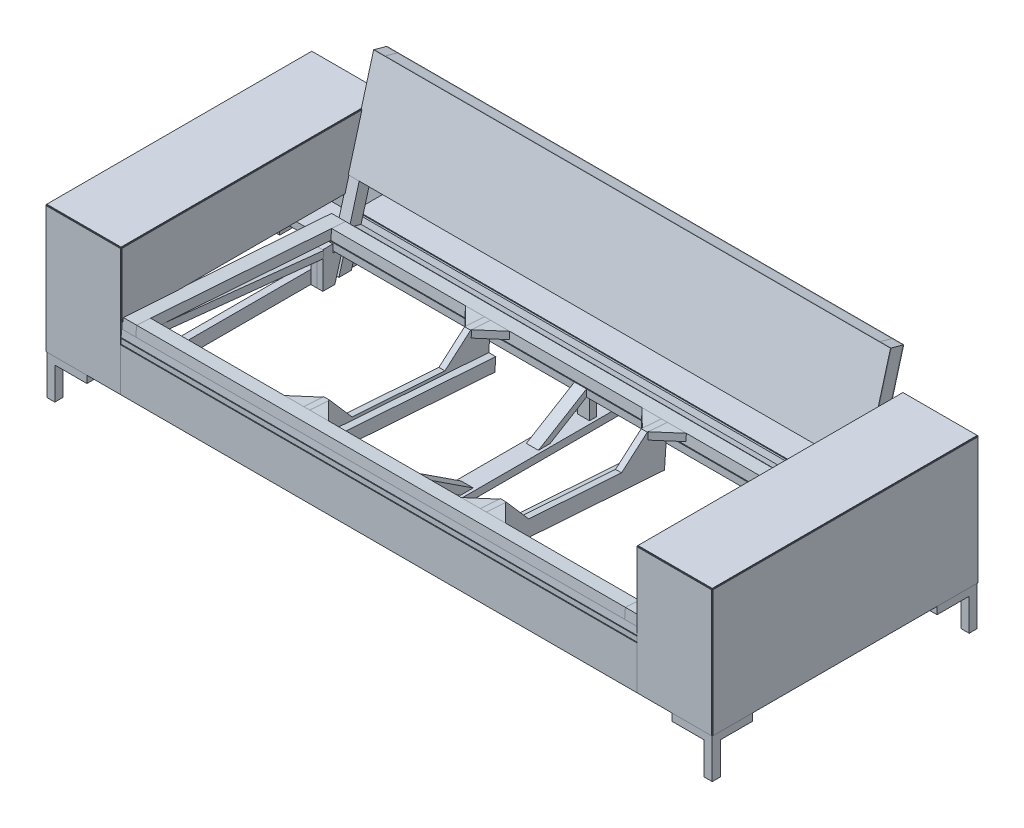
SolidWorks part; units mm, degrees
note: The reader was unsure of these and kept them because the rebuilt part matched: shared geometry of "Sketch1<3>", "Sketch1<4>", "Sketch1<5>", "Sketch4<3>", "Sketch4<4>", "Sketch5<3>", "Sketch5<12>", "Sketch5<4>", "Sketch5<5>", "Sketch5<7>", "Sketch5<8>", "Sketch5<9>", "Sketch5<10>", "Sketch5<11>", "Sketch12<3>", "Sketch14<3>", "Sketch16<3>", "Sketch13<3>", "Sketch13<4>".
other "Foot" parameters "D1"=20.7649, "D2"=44.1105, "D3"=41.275, "D4"=234.95, "D5"=234.95, "D6"=234.95, "D7"=41.275, "D8"=60.325
material "Balsa"
ref_plane "Front Plane" through (0, 0, 0) normal (0, 0, 1) x (1, 0, 0)
ref_plane "Top Plane" through (0, 0, 0) normal (0, 1, 0) x (1, 0, 0)
ref_plane "Right Plane" through (0, 0, 0) normal (1, 0, 0) x (0, 0, -1)
sketch "Sketch1" plane through (0, 0, 0) normal (0, 0, 1) x (1, 0, 0)
  line L0 (0, 0) -> (0, 288750.7845) construction
  line L1 (-817.5625, 0) -> (-1052.5125, 0) construction
  line L2 (-817.5625, 0) -> (-817.5625, 400.05) construction
  line L3 (-817.5625, 400.05) -> (-1052.5125, 400.05) construction
  line L4 (-1052.5125, 0) -> (-1052.5125, 400.05) construction
  line L5 (-1030.2875, 358.775) -> (-1030.2875, 219.075) construction
  line L6 (-1052.5125, 400.05) -> (-1030.2875, 400.05)
  line L7 (-1052.5125, 400.05) -> (-1052.5125, 358.775)
  line L8 (-1052.5125, 358.775) -> (-1030.2875, 358.775)
  line L9 (-1030.2875, 400.05) -> (-1030.2875, 358.775)
  line L10 (-955.675, 400.05) -> (-914.4, 400.05)
  line L11 (-955.675, 400.05) -> (-955.675, 377.825)
  line L12 (-955.675, 377.825) -> (-914.4, 377.825)
  line L13 (-914.4, 400.05) -> (-914.4, 377.825)
  line L14 (-817.5625, 400.05) -> (-839.7875, 400.05)
  line L15 (-817.5625, 400.05) -> (-817.5625, 358.775)
  line L16 (-817.5625, 358.775) -> (-839.7875, 358.775)
  line L17 (-839.7875, 400.05) -> (-839.7875, 358.775)
  line L18 (-1052.5125, 196.85) -> (-1030.2875, 196.85)
  line L19 (-1052.5125, 196.85) -> (-1052.5125, 219.075)
  line L20 (-1052.5125, 219.075) -> (-1030.2875, 219.075)
  line L21 (-1030.2875, 196.85) -> (-1030.2875, 219.075)
  line L22 (-817.5625, 196.85) -> (-839.7875, 196.85)
  line L23 (-817.5625, 196.85) -> (-817.5625, 219.075)
  line L24 (-817.5625, 219.075) -> (-839.7875, 219.075)
  line L25 (-839.7875, 196.85) -> (-839.7875, 219.075)
  line L26 (-1052.5125, 0) -> (-1030.2875, 0)
  line L27 (-1052.5125, 0) -> (-1052.5125, 41.275)
  line L28 (-1052.5125, 41.275) -> (-1030.2875, 41.275)
  line L29 (-1030.2875, 0) -> (-1030.2875, 41.275)
  line L30 (-817.5625, 0) -> (-839.7875, 0)
  line L31 (-817.5625, 0) -> (-817.5625, 41.275)
  line L32 (-817.5625, 41.275) -> (-839.7875, 41.275)
  line L33 (-839.7875, 0) -> (-839.7875, 41.275)
  line L34 (-1030.2875, 196.85) -> (-1030.2875, 41.275) construction
  line L35 (-839.7875, 41.275) -> (-839.7875, 196.85) construction
  line L36 (-839.7875, 219.075) -> (-839.7875, 358.775) construction
  line L37 (-1052.5125, 0) -> (-1052.5125, 400.05)
  line L38 (-839.7875, 0) -> (-1030.2875, 0)
  line L39 (-839.7875, 0) -> (-839.7875, 22.225)
  line L40 (-839.7875, 22.225) -> (-1030.2875, 22.225)
  line L41 (-1030.2875, 0) -> (-1030.2875, 22.225)
  line L42 (-817.5625, 400.05) -> (-1052.5125, 400.05)
  line L43 (-817.5625, 400.05) -> (-817.5625, 196.85)
  point P34 (-935.0375, 400.05)
  dimension "D1" = 22.225
  dimension "D2" = 41.275
  dimension "D3" = 190.5
  dimension "D4" = 400.05
  dimension "D5" = 196.85
  dimension "D6" = 1679.575
  dimension "D7" = 22.225
extrude "Boss-Extrude1" add sketch "Sketch1" along normal blind 838.2 contours L9 L6 L7 L8 | L13 L10 L11 L12 | L14 L17 L16 L15 | L25 L22 L23 L24 | L33 L30 L31 L32 | L26 L29 L28 L27 | L18 L21 L20 L19
extrude "Extrude-Thin1" add sketch "Sketch1<3>" along normal up to surface (838.2 mm away) separate body thin contours L42
sketch "Sketch1<3>" plane through (0, 0, 0) normal (0, 0, 1) x (1, 0, 0) same geometry as "Sketch1"
extrude "Extrude-Thin2" add sketch "Sketch1<4>" along normal up to surface (838.2 mm away) separate body thin contours L37
sketch "Sketch1<4>" plane through (0, 0, 0) normal (0, 0, 1) x (1, 0, 0) same geometry as "Sketch1"
extrude "Extrude-Thin3" add sketch "Sketch1<5>" along normal blind 838.2 separate body thin contours L43
sketch "Sketch1<5>" plane through (0, 0, 0) normal (0, 0, 1) x (1, 0, 0) same geometry as "Sketch1"
sketch "Sketch2" plane through (-817.5625, 0, 0) normal (-1, 0, 0) x (0, 0, 1)
  line L0 (0, 219.075) -> (139.7, 219.075)
  line L1 (838.2, 219.075) -> (0, 219.075) construction
  line L2 (139.7, 219.075) -> (95.25, 358.775)
  line L3 (838.2, 358.775) -> (0, 358.775) construction
  line L4 (95.25, 358.775) -> (0, 358.775)
  line L5 (0, 358.775) -> (0, 219.075)
  dimension "D1" = 95.25
  dimension "D2" = 139.7
extrude "Boss-Extrude2" add sketch "Sketch2" along normal up to surface (22.225 mm away) separate body up to face at (-839.7875, 207.9625, 419.1)
sketch "Sketch3" plane through (0, 400.05, 0) normal (0, -1, 0) x (1, 0, 0)
  line L0 (-839.7875, 838.2) -> (-839.7875, 0) construction
  line L1 (-839.7875, 241.3) -> (-914.4, 241.3)
  line L2 (-839.7875, 241.3) -> (-839.7875, 282.575)
  line L3 (-839.7875, 282.575) -> (-914.4, 282.575)
  line L4 (-914.4, 241.3) -> (-914.4, 282.575)
  line L5 (-914.4, 838.2) -> (-914.4, 0) construction
  line L6 (-955.675, 838.2) -> (-955.675, 0) construction
  line L7 (-955.675, 241.3) -> (-1030.2875, 241.3)
  line L8 (-955.675, 241.3) -> (-955.675, 282.575)
  line L9 (-955.675, 282.575) -> (-1030.2875, 282.575)
  line L10 (-1030.2875, 241.3) -> (-1030.2875, 282.575)
  line L11 (-817.5625, 0) -> (-1052.5125, 0) construction
  line L12 (-839.7875, 584.2) -> (-914.4, 584.2)
  line L13 (-839.7875, 584.2) -> (-839.7875, 625.475)
  line L14 (-839.7875, 625.475) -> (-914.4, 625.475)
  line L15 (-914.4, 584.2) -> (-914.4, 625.475)
  line L16 (-955.675, 584.2) -> (-1030.2875, 584.2)
  line L17 (-955.675, 584.2) -> (-955.675, 625.475)
  line L18 (-955.675, 625.475) -> (-1030.2875, 625.475)
  line L19 (-1030.2875, 584.2) -> (-1030.2875, 625.475)
  line L20 (-1030.2875, 838.2) -> (-1030.2875, 0) construction
  dimension "D1" = 241.3
  dimension "D2" = 584.2
  dimension "D3" = 41.275
extrude "Boss-Extrude3" add sketch "Sketch3" along normal up to surface (22.225 mm away) separate body up to face at (-935.0375, 377.825, 419.1)
sketch "Sketch4" plane through (0, 0, 0) normal (0, -1, 0) x (1, 0, 0)
  line L0 (-839.7875, 838.2) -> (-839.7875, 0) construction
  line L1 (-1030.2875, 838.2) -> (-839.7875, 838.2)
  line L2 (-1030.2875, 838.2) -> (-1030.2875, 727.075)
  line L3 (-1030.2875, 727.075) -> (-839.7875, 727.075)
  line L4 (-839.7875, 838.2) -> (-839.7875, 727.075)
  line L5 (-1030.2875, 838.2) -> (-1030.2875, 0) construction
  line L6 (-839.7875, 0) -> (-1030.2875, 0)
  line L7 (-839.7875, 0) -> (-839.7875, 111.125)
  line L8 (-839.7875, 111.125) -> (-1030.2875, 111.125)
  line L9 (-1030.2875, 0) -> (-1030.2875, 111.125)
  line L10 (-817.5625, 838.2) -> (-1052.5125, 838.2)
  line L11 (-817.5625, 0) -> (-1052.5125, 0)
  line M3 (-1030.2875, 0) -> (-1030.2875, 838.2)
  dimension "D1" = 111.125
extrude "Boss-Extrude4" add sketch "Sketch4" against normal blind 22.225 separate body contours L7 L8 L6 M3 | L4 L1 L3 M3
extrude "Extrude-Thin4" add sketch "Sketch4<3>" against normal up to surface (400.05 mm away) separate body thin contours L10
sketch "Sketch4<3>" plane through (0, 0, 0) normal (0, -1, 0) x (1, 0, 0) same geometry as "Sketch4"
extrude "Extrude-Thin5" add sketch "Sketch4<4>" against normal up to surface (400.05 mm away) separate body thin contours L11
sketch "Sketch4<4>" plane through (0, 0, 0) normal (0, -1, 0) x (1, 0, 0) same geometry as "Sketch4"
mirror "Mirror Arm Geo" about plane through (0, 0, 0) normal (1, 0, 0) of bodies 115 134 103 107 114 104 137 108 135 109 113 111 105 101 133 102 106 110 112
ref_plane "Plane1" through (0, 0, 419.1) normal (0, 0, 1) x (1, 0, 0)
sketch "Sketch5" plane through (-817.5625, 0, 0) normal (1, 0, 0) x (0, 0, -1)
  line L0 (-79.375, 124.2618) -> (-90.3567, 84.4745)
  line L1 (0, 0) -> (-238.125, 0)
  line L2 (0, 0) -> (0, 130.175)
  line L3 (0, 130.175) -> (-238.125, 130.175)
  line L4 (-238.125, 0) -> (-238.125, 130.175)
  line L5 (0, 22.225) -> (-41.275, 22.225)
  line L6 (0, 22.225) -> (0, 0)
  line L7 (0, 0) -> (-41.275, 0)
  line L8 (-41.275, 22.225) -> (-41.275, 0)
  line L9 (0, 130.175) -> (-22.225, 130.175)
  line L10 (0, 130.175) -> (0, 88.9)
  line L11 (0, 88.9) -> (-22.225, 88.9)
  line L12 (-22.225, 130.175) -> (-22.225, 88.9)
  line L13 (-202.474, 91.9539) -> (-161.199, 91.9539)
  line L14 (-202.474, 91.9539) -> (-202.474, 114.1789)
  line L15 (-202.474, 114.1789) -> (-161.199, 114.1789)
  line L16 (-161.199, 91.9539) -> (-161.199, 114.1789)
  line L17 (-79.375, 124.2618) -> (-100.7989, 130.175)
  line L18 (-90.3567, 84.4745) -> (-111.7806, 90.3877)
  line L19 (-100.7989, 130.175) -> (-111.7806, 90.3877)
  line L20 (-144.4255, 9.525) -> (-183.9502, 9.525)
  line L21 (-183.9502, 9.525) -> (-150.6496, 130.175)
  line L22 (-150.6496, 130.175) -> (-113.9229, 120.0381)
  line L23 (-113.9229, 120.0381) -> (-144.4255, 9.525)
  line L24 (-113.9229, 120.0381) -> (-124.9046, 80.2508)
  line L25 (-124.9046, 80.2508) -> (-146.3285, 86.164)
  line L26 (-146.3285, 86.164) -> (-135.3468, 125.9513)
  line L27 (-135.3468, 125.9513) -> (-113.9229, 120.0381)
  line L28 (-200.025, 0) -> (-174.625, 88.9)
  line L29 (-174.625, 88.9) -> (-206.375, 88.9)
  line L30 (-206.375, 88.9) -> (-206.375, 114.1789)
  line L31 (-206.375, 114.1789) -> (-238.125, 114.1789)
  line L32 (-838.2, 0) -> (-838.2, 136.525)
  line L33 (-838.2, 0) -> (-815.975, 0)
  line L34 (-838.2, 0) -> (-838.2, 41.275)
  line L35 (-838.2, 41.275) -> (-815.975, 41.275)
  line L36 (-815.975, 0) -> (-815.975, 41.275)
  line L37 (-838.2, 400.05) -> (-838.2, 196.85) construction
  line L38 (-838.2, 196.85) -> (-838.2, 219.075) construction
  line L39 (-838.2, 154.7295) -> (-240.4418, 92.075)
  line L40 (-815.975, 111.125) -> (-838.2, 111.125)
  line L41 (-815.975, 111.125) -> (-815.975, 152.4)
  line L42 (-815.975, 152.4) -> (-838.2, 152.4)
  line L43 (-838.2, 111.125) -> (-838.2, 152.4)
  line L44 (-838.2, 154.7295) -> (-835.8832, 176.8334)
  line L45 (-240.4418, 92.075) -> (-238.125, 114.1789)
  line L46 (-835.8832, 176.8334) -> (-238.125, 114.1789)
  line L47 (-838.2, 400.05) -> (-838.2, 0) construction
  line L48 (-838.2, 0) -> (0, 0) construction
  line L49 (-815.975, 12.7) -> (-793.75, 12.7)
  line L50 (-815.975, 12.7) -> (-815.975, 150.0705)
  line L51 (-815.975, 150.0705) -> (-793.75, 150.0705)
  line L52 (-793.75, 12.7) -> (-793.75, 150.0705)
  line L53 (-835.8832, 176.8334) -> (-174.625, 130.175)
  line L54 (-835.8832, 176.8334) -> (-833.6429, 208.5834)
  line L55 (-174.625, 130.175) -> (-172.3847, 161.925)
  line L56 (-833.6429, 208.5834) -> (-172.3847, 161.925)
  line L57 (-838.2, 154.7295) -> (-797.1499, 150.4268)
  line L58 (-838.2, 154.7295) -> (-835.8832, 176.8334)
  line L59 (-797.1499, 150.4268) -> (-794.833, 172.5307)
  line L60 (-835.8832, 176.8334) -> (-794.833, 172.5307)
  line L61 (-150.6496, 130.175) -> (-36.7267, 542.925)
  line L62 (-36.7267, 542.925) -> (0, 532.7881)
  line L63 (0, 532.7881) -> (-113.9229, 120.0381)
  line L64 (0, 0) -> (0, 500.445) construction
  line L65 (-838.2, 400.05) -> (0, 400.05) construction
  line L66 (-838.2, 0) -> (0, 0) construction
  point P53 (-107.1867, 130.175)
  point P68 (-192.0022, 91.1104)
  point P69 (-203.7209, 112.4876)
  point P70 (-111.125, 130.175)
  point P71 (0, 0)
  point P72 (-174.625, 130.175)
  point P73 (-238.125, 113.2691)
  line M26 (0, 0) -> (0, 41.275)
  line M27 (0, 41.275) -> (-838.2, 41.275)
  line M28 (-838.2, 41.275) -> (-838.2, 0)
  line M29 (-838.2, 0) -> (0, 0)
  dimension "D1" = 238.125
  dimension "D2" = 130.175
  dimension "D3" = 22.225
  dimension "D4" = 111.125
  dimension "D5" = 142.875
  dimension "D6" = 88.9
  dimension "D7" = 31.75
  dimension "D8" = 38.1
  dimension "D9" = 41.275
  dimension "D10" = 57.15
  dimension "D11" = 9.525
  dimension "D12" = 31.75
  dimension "D13" = 38.1
  dimension "D14" = 92.075
  dimension "D15" = 136.525
  dimension "D16" = 152.4
  dimension "D17" = 12.7
  dimension "D18" = 31.75
  dimension "D19" = 41.275
extrude "Boss-Extrude6" add sketch "Sketch5" along normal blind 19.05 separate body contours L28 L4 M29 M27 | L30 L31 L4 L28 L29 M27 | L28 L1 L8 L5 L2 L23 L20 L21 M27 | L23 L21 L20 M27 | L25 L26 L22 L21 L23 M27 | L31 L30 L29 L28 L21 L13 L14 L15 L16 L3 L4 M27 | L13 L16 L15 L14 | L17 L19 L18 L0 | L26 L25 L23 L22 | L22 L23 L2 L11 L12 L3 L17 L0 L18 L19 M27 | L3 L12 L11 L2 | L5 L8 L1 M26
extrude "Boss-Extrude7" add sketch "Sketch5<3>" along normal blind 19.05 from surface at 19.05 separate body contours L28 L4 M29 M27 | L30 L31 L4 L28 L29 M27 starting at face at (-798.5125, 91.534, 121.7068)
sketch "Sketch5<3>" plane through (-817.5625, 0, 0) normal (1, 0, 0) x (0, 0, -1) same geometry as "Sketch5"
extrude "Boss-Extrude20" add sketch "Sketch5<12>" along normal blind 34.925 separate body contours L63 L62 L61 L3 | L26 L25 L23 L22 | L25 L26 L22 L21 L23 M27 | L23 L21 L20 M27 | L63 L3 L22
sketch "Sketch5<12>" plane through (-817.5625, 0, 0) normal (1, 0, 0) x (0, 0, -1) same geometry as "Sketch5"
extrude "Boss-Extrude9" add sketch "Sketch5<4>" along normal offset from surface (1597.025 mm away) 19.05 from surface at 19.05 separate body contours L5 L8 L1 M26 | L3 L12 L11 L2 | L17 L19 L18 L0 | L13 L16 L15 L14
sketch "Sketch5<4>" plane through (-817.5625, 0, 0) normal (1, 0, 0) x (0, 0, -1) same geometry as "Sketch5"
extrude "Boss-Extrude10" add sketch "Sketch5<5>" along normal offset from surface (1562.1 mm away) 19.05 from surface at 34.925 separate body contours L26 L25 L23 L22 up to face at (798.5125, 107.3248, 95.5778) starting at face at (-782.6375, 273.6908, 91.2756)
sketch "Sketch5<5>" plane through (-817.5625, 0, 0) normal (1, 0, 0) x (0, 0, -1) same geometry as "Sketch5"
extrude "Boss-Extrude11" add sketch "Sketch5<7>" along normal up to surface (1635.125 mm away) separate body contours L36 M29 M27 M28 | L43 L32 L40 L41 L42 | L39 L59 L46 L44 up to face at (817.5625, 20.6375, 419.1)
sketch "Sketch5<7>" plane through (-817.5625, 0, 0) normal (1, 0, 0) x (0, 0, -1) same geometry as "Sketch5"
extrude "Boss-Extrude13" add sketch "Sketch5<8>" along normal blind 41.275 separate body contours L52 L51 L41 L50 M27 | L49 L52 L36 M27
sketch "Sketch5<8>" plane through (-817.5625, 0, 0) normal (1, 0, 0) x (0, 0, -1) same geometry as "Sketch5"
extrude "Extrude-Thin6" add sketch "Sketch5<9>" along normal up to surface (1635.125 mm away) separate body thin contours L32
sketch "Sketch5<9>" plane through (-817.5625, 0, 0) normal (1, 0, 0) x (0, 0, -1) same geometry as "Sketch5"
extrude "Boss-Extrude14" add sketch "Sketch5<10>" along normal blind 41.275 separate body contours L46 L44 L39 L45
sketch "Sketch5<10>" plane through (-817.5625, 0, 0) normal (1, 0, 0) x (0, 0, -1) same geometry as "Sketch5"
extrude "Boss-Extrude15" add sketch "Sketch5<11>" along normal blind 44.45 separate body contours L54 L56 L55 L53
sketch "Sketch5<11>" plane through (-817.5625, 0, 0) normal (1, 0, 0) x (0, 0, -1) same geometry as "Sketch5"
mirror "Mirror2" about plane through (0, 0, 0) normal (1, 0, 0) of bodies 142 144 160 164 166 185 145
sketch "Sketch7" plane through (0, 149.0196, -10.5148) normal (0, 0.9975, -0.0704) x (1, 0, 0)
  line L0 (-773.1125, -846.2565) -> (-773.1125, -183.3543) construction
  line L1 (-773.1125, -846.2565) -> (773.1125, -846.2565)
  line L2 (-773.1125, -846.2565) -> (-773.1125, -801.8065)
  line L3 (-773.1125, -801.8065) -> (773.1125, -801.8065)
  line L4 (773.1125, -846.2565) -> (773.1125, -801.8065)
  line L5 (773.1125, -183.3543) -> (-773.1125, -183.3543)
  line L6 (773.1125, -183.3543) -> (773.1125, -227.8043)
  line L7 (773.1125, -227.8043) -> (-773.1125, -227.8043)
  line L8 (-773.1125, -183.3543) -> (-773.1125, -227.8043)
  line L9 (773.1125, -846.2565) -> (773.1125, -183.3543) construction
  dimension "D1" = 44.45
extrude "Boss-Extrude16" add sketch "Sketch7" against normal up to surface (31.8289 mm away) separate body up to face at (795.3375, 153.5042, 505.2541)
sketch "Sketch8" plane through (-817.5625, 0, 0) normal (-1, 0, 0) x (0, 0, 1)
  line L0 (0, 0) -> (0, 130.175)
  line L1 (0, 0) -> (0, 400.05) construction
  line L2 (0, 130.175) -> (95.25, 130.175)
  line L3 (0, 400.05) -> (0, 0) construction
  line L4 (0, 130.175) -> (111.125, 130.175) construction
  point P6 (0, 132.4753)
  dimension "D1" = 95.25
extrude "Extrude-Thin9" add sketch "Sketch8" against normal up to surface (1635.125 mm away) separate body thin contours L0 L2 up to face at (817.5625, 91.534, 121.7068) thin type one direction reverse wall 2.54
sketch "Sketch12" plane through (-817.5625, 0, 0) normal (-1, 0, 0) x (0, 0, 1)
  line L0 (36.7267, 542.925) -> (42.6399, 521.5011)
  line L1 (183.9502, 9.525) -> (36.7267, 542.925) construction
  line L2 (42.6399, 521.5011) -> (5.9132, 511.3641)
  line L3 (0, 532.7881) -> (144.4255, 9.525) construction
  line L4 (5.9132, 511.3641) -> (0, 532.7881)
  line L5 (0, 532.7881) -> (36.7267, 542.925)
  line L6 (119.5116, 242.99) -> (113.5984, 264.414)
  line L7 (113.5984, 264.414) -> (76.8717, 254.277)
  line L8 (76.8717, 254.277) -> (82.7849, 232.8531)
  line L9 (82.7849, 232.8531) -> (119.5116, 242.99)
  line L10 (119.5116, 242.99) -> (36.7267, 542.925)
  line L11 (0, 532.7881) -> (82.7849, 232.8531)
  line M5 (0, 532.7881) -> (144.4255, 9.525)
  line M7 (183.9502, 9.525) -> (36.7267, 542.925)
  line M8 (36.7267, 542.925) -> (0, 532.7881)
  dimension "D1" = 22.225
  dimension "D2" = 311.15
extrude "Boss-Extrude21" add sketch "Sketch12" against normal up to surface (1565.275 mm away) from surface at -34.925 separate body contours L9 L7 M5 M7 | L2 M7 M8 M5 up to face at (782.6375, 273.6908, 91.2756) starting at face at (-782.6375, 273.6908, 91.2756)
extrude "Extrude-Thin11" add sketch "Sketch12<3>" against normal up to surface (1635.125 mm away) separate body thin contours L10 | L11
sketch "Sketch12<3>" plane through (-817.5625, 0, 0) normal (-1, 0, 0) x (0, 0, 1) same geometry as "Sketch12"
ref_plane "Plane2" through (-269.875, 0, 0) normal (1, 0, 0) x (0, 0, -1)
sketch "Sketch14" plane through (-269.875, 0, 0) normal (1, 0, 0) x (0, 0, -1)
  line L0 (-789.3031, 205.4548) -> (-798.242, 78.7698)
  line L1 (-798.242, 78.7698) -> (-225.6634, 38.3686)
  line L2 (-225.6634, 38.3686) -> (-216.7245, 165.0536)
  line L3 (-216.7245, 165.0536) -> (-280.067, 169.5231)
  line L4 (-833.6429, 208.5834) -> (-172.3847, 161.925) construction
  line L5 (-280.067, 169.5231) -> (-361.4414, 98.8754)
  line L6 (-361.4414, 98.8754) -> (-655.3129, 119.611)
  line L7 (-655.3129, 119.611) -> (-725.9606, 200.9854)
  line L8 (-725.9606, 200.9854) -> (-789.3031, 205.4548)
  line L9 (-511.9527, 58.5692) -> (-508.3771, 109.2432) construction
  line L10 (-798.242, 78.7698) -> (-225.6634, 38.3686)
  line L11 (-798.242, 78.7698) -> (-795.3369, 119.9424)
  line L12 (-225.6634, 38.3686) -> (-222.7582, 79.5412)
  line L13 (-795.3369, 119.9424) -> (-222.7582, 79.5412)
  dimension "D1" = 127
  dimension "D2" = 50.8
  dimension "D3" = 45
  dimension "D4" = 63.5
  dimension "D5" = 41.275
extrude "Boss-Extrude25" add sketch "Sketch14" against normal blind 19.05 separate body contours L13 L9 L6 L7 L8 L0 | L1 L9 L13 L0 | L9 L10 L2 L13 | L9 L13 L2 L3 L5 L6
extrude "Boss-Extrude26" add sketch "Sketch14<3>" along normal blind 22.225 separate body contours L1 L9 L13 L0 | L9 L10 L2 L13
sketch "Sketch14<3>" plane through (-269.875, 0, 0) normal (1, 0, 0) x (0, 0, -1) same geometry as "Sketch14"
sketch "Sketch15" plane through (0, 149.0196, -10.5148) normal (0, 0.9975, -0.0704) x (1, 0, 0)
  line L0 (-288.925, -227.8043) -> (-349.25, -227.8043)
  line L1 (-773.1125, -227.8043) -> (773.1125, -227.8043) construction
  line L2 (-349.25, -227.8043) -> (-288.925, -288.1293)
  line L3 (-288.925, -291.3043) -> (-288.925, -367.5043) construction
  line L4 (-288.925, -288.1293) -> (-288.925, -227.8043)
  line L5 (-269.875, -227.8043) -> (-209.55, -227.8043)
  line L6 (-209.55, -227.8043) -> (-269.875, -288.1293)
  line L8 (-269.875, -288.1293) -> (-269.875, -227.8043)
  line L9 (-269.875, -801.8065) -> (-269.875, -741.4815)
  line L10 (-269.875, -662.1065) -> (-269.875, -738.3065) construction
  line L11 (-269.875, -741.4815) -> (-209.55, -801.8065)
  line L12 (773.1125, -801.8065) -> (-773.1125, -801.8065) construction
  line L13 (-209.55, -801.8065) -> (-269.875, -801.8065)
  line L14 (-288.925, -801.8065) -> (-349.25, -801.8065)
  line L15 (-349.25, -801.8065) -> (-288.925, -741.4815)
  line L16 (-288.925, -741.4815) -> (-288.925, -801.8065)
  line L17 (-269.875, -801.8065) -> (-269.875, -227.8043) construction
  point P12 (-269.875, -293.83)
  dimension "D1" = 60.325
extrude "Boss-Extrude27" add sketch "Sketch15" against normal blind 22.225 separate body
mirror "Mirror6" about plane through (0, 0, 0) normal (1, 0, 0) of bodies 201 200 203 202 204 205
sketch "Sketch16" plane through (0, 0, 0) normal (1, 0, 0) x (0, 0, -1)
  line L0 (-161.199, 91.9539) -> (-202.474, 91.9539) construction
  line L1 (-815.975, 0) -> (-41.275, 0)
  line L2 (-815.975, 0) -> (-815.975, 22.225)
  line L3 (-815.975, 22.225) -> (-41.275, 22.225)
  line L4 (-41.275, 0) -> (-41.275, 22.225)
  line L5 (-170.724, 22.225) -> (-192.949, 22.225)
  line L6 (-170.724, 22.225) -> (-170.724, 91.9539)
  line L7 (-170.724, 91.9539) -> (-192.949, 91.9539)
  line L8 (-192.949, 22.225) -> (-192.949, 91.9539)
  line L9 (-161.199, 91.9539) -> (-202.474, 91.9539) construction
  line L10 (-560.7996, 22.225) -> (-601.3694, 22.225)
  line L11 (-601.3694, 22.225) -> (-797.1499, 150.4268)
  line L12 (-797.1499, 150.4268) -> (-794.5442, 175.2866)
  line L13 (-794.5442, 175.2866) -> (-560.7996, 22.225)
  line L14 (-317.8689, 22.225) -> (-202.474, 91.9539)
  line L15 (-202.474, 91.9539) -> (-202.474, 114.1789)
  line L16 (-202.474, 114.1789) -> (-354.6493, 22.225)
  line L17 (-354.6493, 22.225) -> (-317.8689, 22.225)
  line L18 (-797.1499, 150.4268) -> (-794.833, 172.5307) construction
  line L19 (-797.1499, 150.4268) -> (-794.833, 172.5307) construction
  point P15 (-216.0699, 109.5352)
  point P16 (-181.8365, 91.9539)
  point P20 (-794.9706, 175.584)
  point P24 (0, 0)
  point P25 (-201.5531, 91.9539)
  point P26 (-202.474, 114.1789)
  point P28 (0, 0)
  dimension "D1" = 22.225
  dimension "D2" = 22.225
  dimension "D3" = 177.8
  dimension "D4" = 279.4
extrude "Boss-Extrude28" add sketch "Sketch16" along normal mid plane 57.15 separate body contours L3 L4 L1 L2
extrude "Boss-Extrude29" add sketch "Sketch16<3>" along normal mid plane 38.1 separate body contours L13 L12 L11 L3 | L15 L16 L3 L14 | L8 L3 L6 L7
sketch "Sketch16<3>" plane through (0, 0, 0) normal (1, 0, 0) x (0, 0, -1) same geometry as "Sketch16"
sketch "Sketch13" plane through (0, 0, 0) normal (0, -1, 0) x (1, 0, 0)
  line L0 (-1052.5125, 838.2) -> (-925.5125, 838.2)
  line L1 (-1030.2875, 838.2) -> (-839.7875, 838.2) construction
  line L2 (-925.5125, 838.2) -> (-925.5125, 812.8)
  line L3 (-925.5125, 812.8) -> (-1027.1125, 812.8)
  line L4 (-1027.1125, 812.8) -> (-1027.1125, 711.2)
  line L5 (-1027.1125, 711.2) -> (-1052.5125, 711.2)
  line L6 (-1052.5125, 838.2) -> (-1052.5125, 0) construction
  line L7 (-1052.5125, 711.2) -> (-1052.5125, 838.2)
  line L8 (-933.45, 812.8) -> (-1027.1125, 719.1375)
  line L9 (-1027.1125, 812.8) -> (-1052.5125, 812.8)
  line L10 (-1027.1125, 812.8) -> (-1027.1125, 838.2)
  line L11 (-1027.1125, 838.2) -> (-1052.5125, 838.2)
  line L12 (-1052.5125, 812.8) -> (-1052.5125, 838.2)
  line L13 (-1016.1905, 741.553) -> (-1016.1905, 801.878) construction
  line L14 (-1016.1905, 801.878) -> (-955.8655, 801.878) construction
  circle A0 centre (-1016.1905, 801.878) radius 2.4892
  circle A1 centre (-955.8655, 801.878) radius 2.4892
  circle A2 centre (-1016.1905, 741.553) radius 2.4892
  line M10 (-1030.2875, 0) -> (-1030.2875, 838.2)
  line M11 (-1030.2875, 838.2) -> (-1052.5125, 838.2)
  line M12 (-1052.5125, 838.2) -> (-1052.5125, 0)
  dimension "D5" = 4.9784
  dimension "D1" = 25.4
  dimension "D2" = 127
  dimension "D3" = 93.6625
  dimension "D4" = 93.6625
  dimension "D6" = 60.325
  dimension "D7" = 36.322
  dimension "D8" = 36.322
extrude "Boss-Extrude22" add sketch "Sketch13" along normal blind 25.4 separate body contours L9 L7 L5 M10 | L9 M10 M11 M12 | L10 L3 L2 L0 | L4 L9 L5 M10 | L9 L10 L0 M10
extrude "Boss-Extrude23" add sketch "Sketch13<3>" along normal blind 2.032 from offset 0.508 contours L8 L3 L4 A2 A1 A0
sketch "Sketch13<3>" plane through (0, 0, 0) normal (0, -1, 0) x (1, 0, 0) same geometry as "Sketch13"
extrude "Boss-Extrude24" add sketch "Sketch13<4>" along normal blind 127 contours L9 M10 M11 M12 | L9 L10 L0 M10
sketch "Sketch13<4>" plane through (0, 0, 0) normal (0, -1, 0) x (1, 0, 0) same geometry as "Sketch13"
chamfer "Chamfer1" distance 1.27 angle 45 3 edges at (-1013.7013, -2.54, 741.553) (-953.3763, -2.54, 801.878) (-1013.7013, -2.54, 801.878)
mirror "Mirror4" about plane through (0, 0, 0) normal (1, 0, 0) of bodies 196
mirror "Mirror5" about plane through (0, 0, 419.1) normal (0, 0, 1) of bodies 196 197
equation "\"D7@Sketch1\"=\"D1@Sketch1\""
equation "\"D4@Sketch13\"=\"D3@Sketch13\""
equation "\"D8@Sketch13\"=\"D7@Sketch13\""
equation "\"D2@Sketch16\"=\"D1@Sketch16\""
